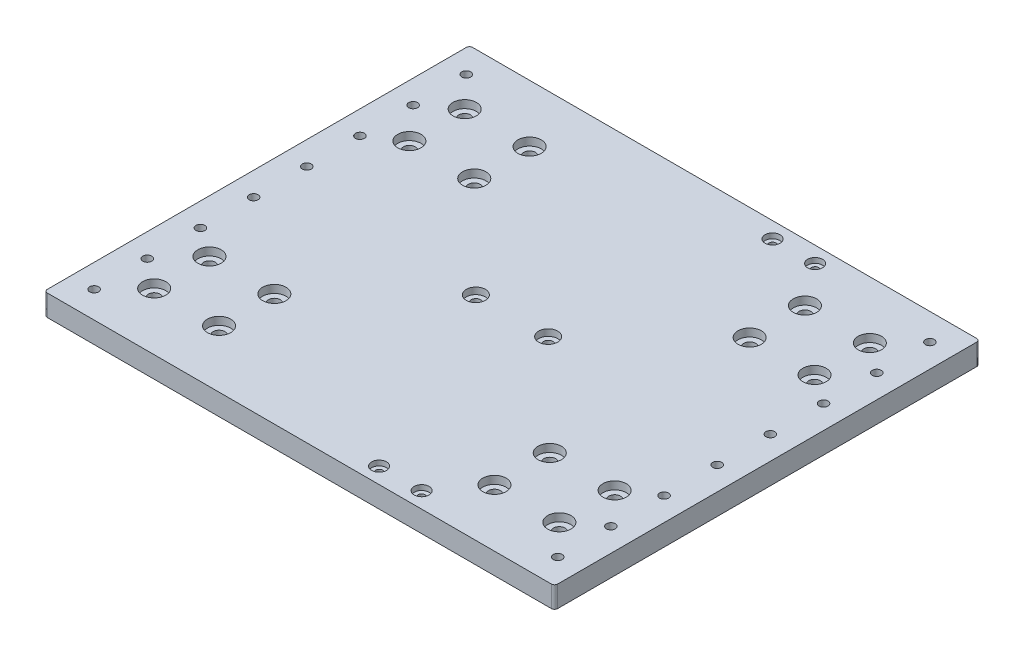
SolidWorks part; units mm, degrees
ref_plane "Front Plane" through (0, 0, 0) normal (0, 0, 1) x (1, 0, 0)
ref_plane "Top Plane" through (0, 0, 0) normal (0, 1, 0) x (1, 0, 0)
ref_plane "Right Plane" through (0, 0, 0) normal (1, 0, 0) x (0, 0, -1)
sketch "Sketch1" plane through (0, 0, 0) normal (0, 1, 0) x (1, 0, 0)
  line L1 (-120, -100) -> (120, -100)
  line L2 (-120, -100) -> (-120, 100)
  line L3 (-120, 100) -> (120, 100)
  line L4 (120, -100) -> (120, 100)
  line L5 (-120, -100) -> (120, 100) construction
  line L6 (-120, 100) -> (120, -100) construction
  point P0 (0, 0)
  dimension "D1" = 240
  dimension "D2" = 200
extrude "Boss-Extrude1" add sketch "Sketch1" along normal mid plane 10
hole_wizard "CBORE for M5 Pan Head Machine Screw1" positions "Sketch11" profile "Sketch10" counterbore size "M5" standard "ANSI Metric" end condition through all
sketch "Sketch11" plane through (66.9231, 5, -81.9693) normal (0, -1, 0) x (-1, 0, 0)
  line L0 (146.9231, -1018.8886) -> (146.9231, 48981.1114) construction
  line L1 (-912.3245, -141.9693) -> (49087.6755, -141.9693) construction
  line L2 (186.9231, 18.0307) -> (186.9231, -181.9693) construction
  line L3 (186.9231, -181.9693) -> (-53.0769, -181.9693) construction
  line L5 (162.1731, -128.9693) -> (131.6731, -128.9693) construction
  line L6 (162.1731, -128.9693) -> (162.1731, -154.9693) construction
  line L7 (162.1731, -154.9693) -> (131.6731, -154.9693) construction
  line L8 (131.6731, -128.9693) -> (131.6731, -154.9693) construction
  line L9 (162.1731, -128.9693) -> (131.6731, -154.9693) construction
  line L10 (162.1731, -154.9693) -> (131.6731, -128.9693) construction
  point P0 (162.1731, -154.9693)
  point P2 (131.6731, -154.9693)
  point P4 (131.6731, -128.9693)
  point P6 (162.1731, -128.9693)
  dimension "D1" = 40
  dimension "D2" = 40
  dimension "D3" = 15.25
  dimension "D4" = 26
  dimension "D5" = 13
  dimension "D6" = 30.5
sketch "Sketch10" plane through (-95.25, 5, 73) normal (1, 0, 0) x (0, 0, 1)
  line L0 (0, 0) -> (0, 10)
  line L1 (0, 10) -> (2.75, 10)
  line L3 (2.75, 10) -> (2.75, 3.7)
  line L4 (2.75, 3.7) -> (5.5, 3.7)
  line L5 (5.5, 3.7) -> (5.5, 0)
  line L7 (5.5, 0) -> (0, 0)
  line L11 (0, -6.35) -> (0, 107.95) construction
  dimension "Thru Hole Dia." = 5.5
  dimension "Thru Hole Depth" = 10
  dimension "C'Bore Dia." = 11
  dimension "C'Bore Depth" = 3.7
mirror "Mirror1" about plane through (0, 0, 0) normal (1, 0, 0) of "CBORE for M5 Pan Head Machine Screw1"
mirror "Mirror2" about plane through (0, 0, 0) normal (0, 0, 1) of "Mirror1"
hole_wizard "CBORE for M4 Pan Head Machine Screw1" positions "Sketch9" profile "Sketch8" counterbore size "M4" standard "ANSI Metric" end condition through all
sketch "Sketch9" plane through (-30.3385, 5, -23.5385) normal (0, -1, 0) x (-1, 0, 0)
  line L0 (-1000, -23.5385) -> (49000, -23.5385) construction
  point P0 (-13.3385, -23.5385)
  point P2 (-47.3385, -23.5385)
  dimension "D1" = 17
  dimension "D2" = 17
sketch "Sketch8" plane through (-17, 5, 0) normal (1, 0, 0) x (0, 0, 1)
  line L0 (0, 0) -> (0, 10)
  line L1 (0, 10) -> (2.25, 10)
  line L3 (2.25, 10) -> (2.25, 3.1)
  line L4 (2.25, 3.1) -> (4.5, 3.1)
  line L5 (4.5, 3.1) -> (4.5, 0)
  line L7 (4.5, 0) -> (0, 0)
  line L11 (0, -6.35) -> (0, 107.95) construction
  dimension "Thru Hole Dia." = 4.5
  dimension "Thru Hole Depth" = 10
  dimension "C'Bore Dia." = 9
  dimension "C'Bore Depth" = 3.1
hole_wizard "M5x0.8 Tapped Hole1" positions "Sketch7" profile "Sketch5" tap size "M5x0.8" standard "ANSI Metric" end condition through all
sketch "Sketch7" plane through (0, 5, 0) normal (0, 1, 0) x (1, 0, 0)
  line L0 (120, 100) -> (-120, 100) construction
  line L1 (-120, 100) -> (-120, -100) construction
  line L2 (120, -100) -> (120, 100) construction
  point P0 (-109, 87.5)
  point P2 (109, 87.5)
  dimension "D1" = 12.5
  dimension "D2" = 11
  dimension "D3" = 11
  dimension "D4" = 12.5
sketch "Sketch5" plane through (-109, 5, -87.5) normal (1, 0, 0) x (0, 0, 1)
  line L0 (0, 0) -> (0, 10)
  line L1 (0, 10) -> (2.1, 10)
  line L2 (2.1, 10) -> (2.1, 0)
  line L5 (2.1, 0) -> (0, 0)
  line L11 (0, -6.35) -> (0, 107.95) construction
  dimension "Thru Tap Drill Dia." = 4.2
  dimension "Thru Tap Drill Depth" = 10
cosmetic thread "Hole Thread1" parameters "D2"=5
cosmetic thread "Hole Thread2" parameters "D2"=5
fillet "Fillet1" radius 1.5 4 edges at (-120, 0, -100) (120, 0, -100) (-120, 0, 100) (120, 0, 100)
pattern_linear "LPattern2" count 8 spacing 25 along (0, 0, 1) of "M5x0.8 Tapped Hole1"
hole_wizard "CBORE for M3 Pan Head Machine Screw1" positions "Sketch13" profile "Sketch12" counterbore size "M3" standard "ANSI Metric" end condition through all
sketch "Sketch13" plane through (0, 5, 0) normal (0, 1, 0) x (1, 0, 0)
  line L0 (118.5, 100) -> (-118.5, 100) construction
  point P0 (30, 92.5)
  point P2 (50, 92.5)
  dimension "D1" = 50
  dimension "D2" = 20
  dimension "D3" = 7.5
  dimension "D4" = 7.5
sketch "Sketch12" plane through (30, 5, -92.5) normal (1, 0, 0) x (0, 0, 1)
  line L0 (0, 0) -> (0, 10)
  line L1 (0, 10) -> (1.6, 10)
  line L3 (1.6, 10) -> (1.6, 2.4)
  line L4 (1.6, 2.4) -> (3.5, 2.4)
  line L5 (3.5, 2.4) -> (3.5, 0)
  line L7 (3.5, 0) -> (0, 0)
  line L11 (0, -6.35) -> (0, 107.95) construction
  dimension "Thru Hole Dia." = 3.2
  dimension "Thru Hole Depth" = 10
  dimension "C'Bore Dia." = 7
  dimension "C'Bore Depth" = 2.4
mirror "Mirror3" about plane through (0, 0, 0) normal (0, 0, 1) of "CBORE for M3 Pan Head Machine Screw1"
